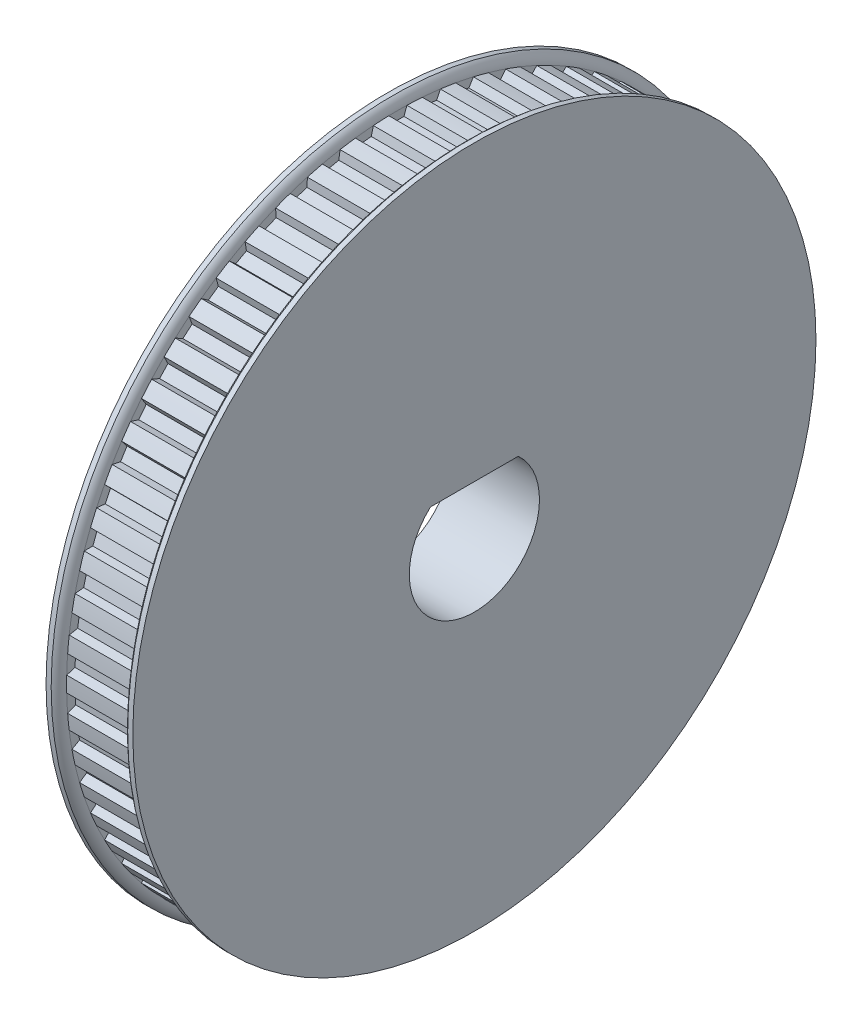
SolidWorks part; units mm, degrees
ref_plane "Front Plane" through (0, 0, 0) normal (0, 0, 1) x (1, 0, 0)
ref_plane "Top Plane" through (0, 0, 0) normal (0, 1, 0) x (1, 0, 0)
ref_plane "Right Plane" through (0, 0, 0) normal (1, 0, 0) x (0, 0, -1)
sketch "Sketch1" plane through (0, 0, 0) normal (1, 0, 0) x (0, 0, -1)
  line L3 (0, 0) -> (0, 51.285) construction
  line L6 (0, 51.285) -> (0, 52.485) construction
  line L7 (-1.325, 52.4683) -> (-0.8915, 51.2773)
  line L8 (1.325, 52.4683) -> (0.8915, 51.2773)
  line L9 (0, -2.2) -> (0, -3.2) construction
  line L10 (0, 52.985) -> (0, 52.485) construction
  line L12 (-0.8915, 51.2773) -> (0.8915, 51.2773)
  line L15 (0, 0) -> (0, -2.2) construction
  circle A0 centre (0, 0) radius 52.985 construction
  circle A1 centre (0, 0) radius 51.285 construction
  arc A7 (1.325, 52.4683) -> (-1.325, 52.4683) centre (0, 0) ccw
  dimension "PD" = 105.97
  dimension "D1" = 40
  dimension "D3" = 0.5
  dimension "D2" = 1.2
  dimension "D4" = 2.65
sketch "Sketch2" plane through (0, 0, 0) normal (0, 0, 1) x (1, 0, 0)
  line L0 (-10.5, 0) -> (10.5, 0) construction
  line L1 (-10.5, 4) -> (10.5, 4) construction
  line L2 (-10.5, 4) -> (-10.5, 19) construction
  line L3 (-2.2, 54) -> (-1.45, 54)
  line L4 (-0.7, 52.485) -> (-2.2, 52.485) construction
  line L5 (9.75, 52.485) -> (9.75, 54) construction
  line L6 (-0.7, 52.485) -> (9, 52.485)
  line L7 (-2.2, 19) -> (-2.2, 4)
  line L8 (9, 52.485) -> (10.5, 52.485) construction
  line L9 (9.75, 54) -> (10.5, 54)
  line L10 (10.5, 54) -> (10.5, 4)
  line L11 (-2.2, 4) -> (10.5, 4)
  line L12 (-6.35, 19) -> (-6.35, 4) construction
  line L13 (-2.2, 54) -> (-2.2, 19)
  line L14 (-2.2, 19) -> (-10.5, 19) construction
  arc A0 (9, 52.485) -> (9.75, 54) centre (10.9052, 52.485) cw
  arc A1 (-0.7, 52.485) -> (-1.45, 54) centre (-2.6052, 52.485) ccw
  point P19 (-0.7, 52.485)
  point P20 (9, 52.485)
  dimension "Bore Size" = 4
  dimension "Overall Width" = 21
  dimension "Inside Width" = 9.7
  dimension "Outside Width" = 12.7
  dimension "Hub Dia" = 19
  dimension "OD" = 108
sketch "Sketch6" plane through (0, 0, 0) normal (0, 0, 1) x (1, 0, 0)
  line L0 (9.75, 54) -> (10.5, 54) construction
  line L1 (-0.7, 52.485) -> (9, 52.485) construction
  line L2 (-2.2, 54) -> (-1.45, 54) construction
  line L3 (-2.2, 54) -> (-2.2, 19) construction
  line L4 (-2.2, 19) -> (-10.5, 19) construction
  line L5 (-10.5, 4) -> (-10.5, 19) construction
  line L6 (-10.5, 4) -> (10.5, 4) construction
  line L7 (10.5, 54) -> (10.5, 4) construction
  line L8 (9.75, 54) -> (10.5, 54)
  line L9 (-0.7, 52.485) -> (9, 52.485)
  line L10 (-2.2, 54) -> (-1.45, 54)
  line L11 (-2.2, 54) -> (-2.2, 19)
  line L12 (-2.2, 19) -> (-10.5, 19)
  line L13 (-10.5, 4) -> (-10.5, 19)
  line L14 (-10.5, 4) -> (10.5, 4)
  line L15 (10.5, 54) -> (10.5, 4)
  line L16 (-2.2, 19) -> (-2.2, 4)
  arc A0 (9.75, 54) -> (9, 52.485) centre (10.9052, 52.485) ccw construction
  arc A1 (-0.7, 52.485) -> (-1.45, 54) centre (-2.6052, 52.485) ccw construction
  arc A2 (9.75, 54) -> (9, 52.485) centre (10.9052, 52.485) ccw
  arc A3 (-0.7, 52.485) -> (-1.45, 54) centre (-2.6052, 52.485) ccw
revolve "Revolve1" add sketch "Sketch6" angle 360 about L14 region at (4.15, 28.3978, 0)
sketch "Sketch3" plane through (0, 0, 0) normal (1, 0, 0) x (0, 0, -1)
  line L2 (-1.325, 52.4683) -> (-0.8915, 51.2773) construction
  line L3 (-0.8915, 51.2773) -> (0.8915, 51.2773) construction
  line L4 (1.325, 52.4683) -> (0.8915, 51.2773) construction
  line L5 (-1.325, 52.4683) -> (-0.8915, 51.2773)
  line L6 (-0.8915, 51.2773) -> (0.8915, 51.2773)
  line L7 (1.325, 52.4683) -> (0.8915, 51.2773)
  arc A1 (1.325, 52.4683) -> (-1.325, 52.4683) centre (0, 0) ccw construction
  arc A2 (1.325, 52.4683) -> (-1.325, 52.4683) centre (0, 0) ccw
extrude "Cut-Extrude1" cut sketch "Sketch3" along normal up to vertex (9 mm away) from vertex up to point (9, 52.485, 0) starting at point (-0.7, 52.485, 0)
pattern_circular "CirPattern1" count 62 over 360 about axis through (-10.5, 4, 0) along (-1, 0, 0) of "Cut-Extrude1"
sketch "Sketch5" plane through (0, 0, 0) normal (0, 0, 1) x (1, 0, 0)
  line L0 (-10.5, 0) -> (10.5, 0) construction
  point P0 (9, 0)
sketch "Sketch8" plane through (-2.2, 0, 0) normal (-1, 0, 0) x (0, 0, 1)
  line L0 (-6.4323, 11.025) -> (6.4323, 11.025)
  arc A0 (-6.4323, 11.025) -> (6.4323, 11.025) centre (0, 4) ccw
  circle A1 centre (0, 4) radius 50 construction
  dimension "D1" = 19.05
  dimension "D2" = 7.025
extrude "Cut-Extrude2" cut sketch "Sketch8" against normal through all
equation "\"D3@Sketch1\" = \"ht@Sketch1\" / 2"
equation "\"D2@Sketch1\" = \"hs@Sketch1\" - \"ht@Sketch1\""
